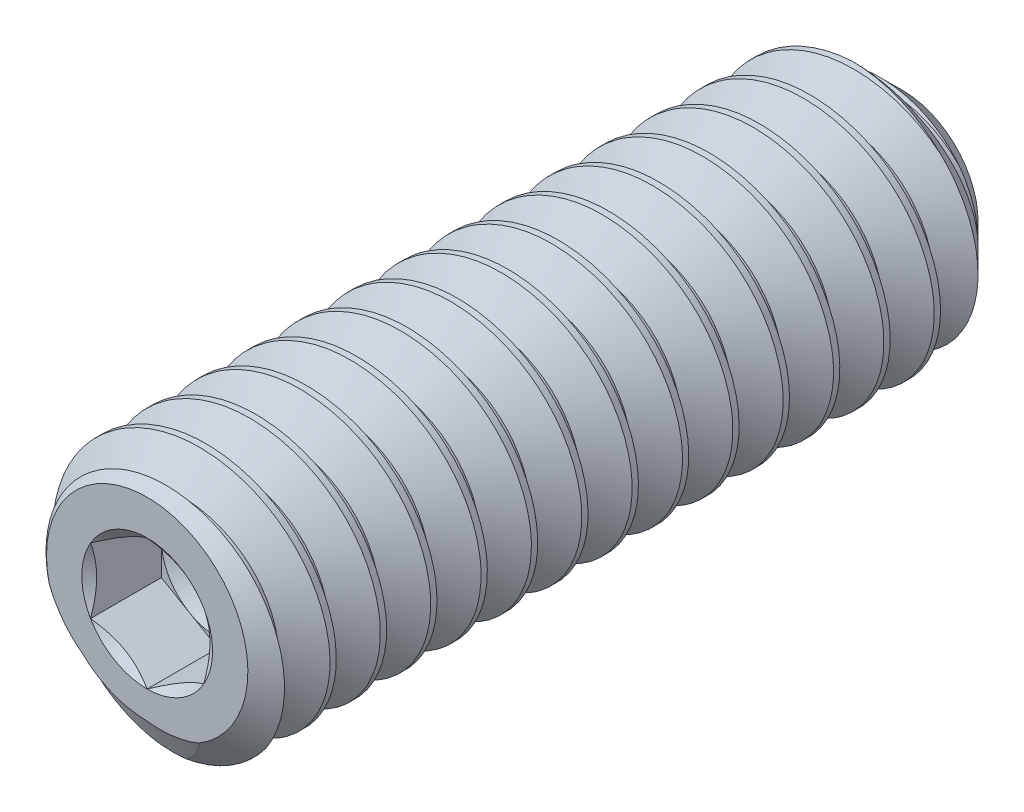
SolidWorks part; units mm, degrees
ref_plane "Front" through (0, 0, 0) normal (0, 0, 1) x (1, 0, 0)
ref_plane "Top" through (0, 0, 0) normal (0, 1, 0) x (1, 0, 0)
ref_plane "Right" through (0, 0, 0) normal (1, 0, 0) x (0, 0, -1)
sketch "Sketch22" plane through (0, 0, 0) normal (1, 0, 0) x (0, 0, -1)
  line L0 (-3, 0) -> (-3, 0.8)
  line L1 (-3, 0.8) -> (-2.86, 1)
  line L2 (-2.86, 1) -> (2.6, 1)
  line L3 (2.6, 1) -> (3, 0.6)
  line L4 (-0.13, 1) -> (-0.13, -1) construction
  line L5 (3, 0) -> (-3, 0)
  line L6 (-3, 0.8) -> (-3, -0.8) construction
  line L7 (3, 0) -> (3, 0.6)
  point P11 (-0.13, 0)
  dimension "D1" = 1.6
  dimension "Dia" = 2
  dimension "D2" = 0.4
  dimension "Length" = 6
  dimension "D3" = 35
  dimension "D6" = 45
revolve "Revolve1" add sketch "Sketch22" angle 360 about L5
ref_plane "Plane1" through (0, 0, -3) normal (0, 0, 1) x (1, 0, 0)
sketch "Sketch27" plane through (0, 0, -3) normal (0, 0, 1) x (1, 0, 0)
  circle A0 centre (0, 0) radius 1 construction
  circle A1 centre (0, 0) radius 1
curve "Helix/Spiral1" pitch 0.4 height 6.4 radius 1 centre (0, 0, -3) axis (0, 0, 1) start towards (0, 1, 0)
sketch "Sketch28" plane through (0, 0, 0) normal (1, 0, 0) x (0, 0, -1)
  line L0 (3, 1) -> (3.35, 1)
  line L1 (3.35, 1) -> (3.2, 0.7402)
  line L2 (3.2, 0.7402) -> (3.15, 0.7402)
  line L3 (3.15, 0.7402) -> (3, 1)
  line L4 (3.075, 0.8701) -> (3.275, 0.8701) construction
  line L6 (-2.86, 1) -> (2.6, 1) construction
  dimension "D1" = 0.05
  dimension "D2" = 0.2
  dimension "D3" = 60
sweep "Cut-Sweep2" cut profiles "Sketch28" path "Helix/Spiral1" align with end faces yes
sketch "Sketch23" plane through (0, 0, 3) normal (0, 0, 1) x (1, 0, 0)
  line L1 (0, 0.5196) -> (-0.45, 0.2598)
  line L2 (-0.45, 0.2598) -> (-0.45, -0.2598)
  line L3 (-0.45, -0.2598) -> (0, -0.5196)
  line L4 (0, -0.5196) -> (0.45, -0.2598)
  line L5 (0.45, -0.2598) -> (0.45, 0.2598)
  line L6 (0.45, 0.2598) -> (0, 0.5196)
  circle A0 centre (0, 0) radius 0.45 construction
  dimension "Hex" = 0.9
extrude "Cut-Extrude10" cut sketch "Sketch23" against normal blind 0.5625
sketch "Sketch24" plane through (0, 0, 3) normal (0, 0, 1) x (1, 0, 0)
  circle A0 centre (0, 0) radius 0.5196
extrude "Cut-Extrude11" cut sketch "Sketch24" against normal through all draft 55
sketch "Sketch26" plane through (0, 0, 2.4375) normal (0, 0, 1) x (1, 0, 0)
  circle A0 centre (0, 0) radius 0.45 construction
  circle A1 centre (0, 0) radius 0.45
extrude "Cut-Extrude12" cut sketch "Sketch26" against normal through all draft 60
sketch "Sketch30" plane through (0, 0, 0) normal (1, 0, 0) x (0, 0, -1)
  line L0 (-2.86, 1) -> (2.6, 1) construction
  line L1 (-3, 0) -> (-3, 0.8) construction
  line L2 (3, 0) -> (3, 0.6) construction
  point P0 (-3, 1)
  point P1 (3, 1)
  point P2 (3, -1)
  point P11 (2, -1)
  dimension "D1" = 1
equation "\"D1@Sketch28\" = \"D4@Helix/Spiral1\" * .125"
equation "\"D2@Sketch28\" = \"D4@Helix/Spiral1\" * .5"
equation "\"D3@Helix/Spiral1\" = \"Length@Sketch22\" + \"D4@Helix/Spiral1\""
equation "\"D1@Sketch30\" = \"D4@Helix/Spiral1\" * 2.5"
equation "\"hex Depth@Cut-Extrude10\" = \"Hex@Sketch23\" * .625"
equation "\"D1@Sketch22\" = \"Dia@Sketch22\" * .8"
equation "\"D2@Sketch22\" = \"D4@Helix/Spiral1\""
